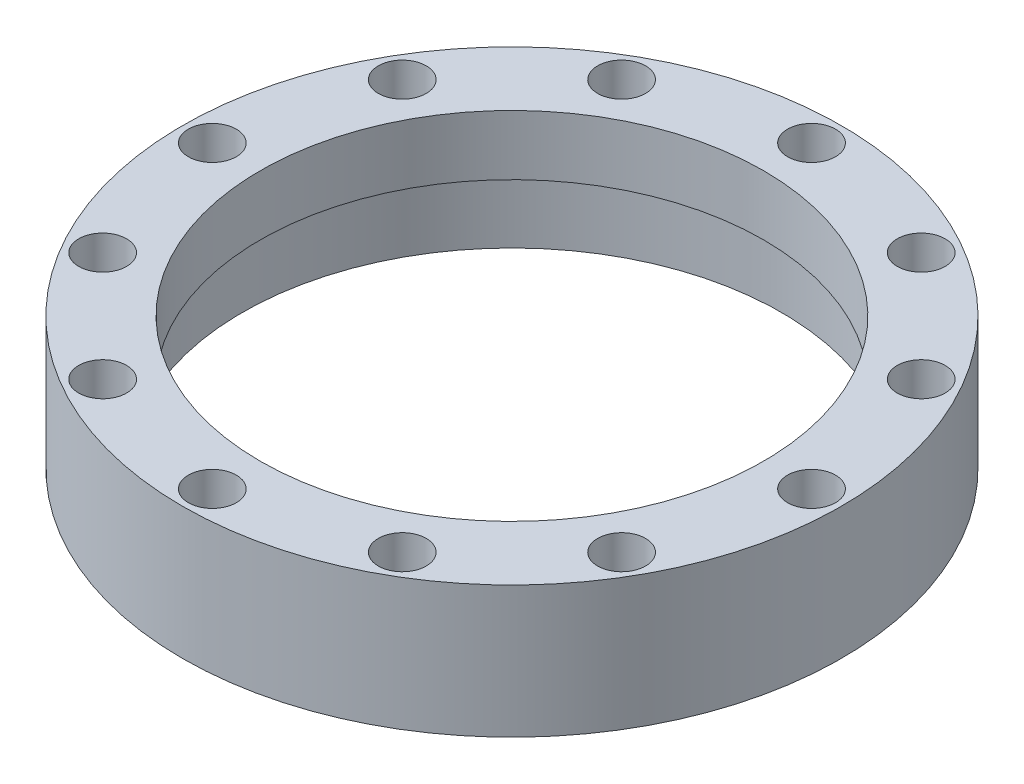
SolidWorks part; units mm, degrees
ref_plane "Front Plane" through (0, 0, 0) normal (0, 0, 1) x (1, 0, 0)
ref_plane "Top Plane" through (0, 0, 0) normal (0, 1, 0) x (1, 0, 0)
ref_plane "Right Plane" through (0, 0, 0) normal (1, 0, 0) x (0, 0, -1)
sketch "Sketch1" plane through (0, 0, 0) normal (0, 1, 0) x (1, 0, 0)
  line L0 (0, 48.2621) -> (0, -49.945) construction
  circle A0 centre (0, 0) radius 27.5
  circle A1 centre (0, 0) radius 25 construction
  circle A2 centre (0, 0) radius 22.5
  circle A3 centre (0, 25) radius 1.5
  circle A4 centre (12.5, 21.6506) radius 1.5
  circle A5 centre (21.6506, 12.5) radius 1.5
  circle A6 centre (25, 0) radius 1.5
  circle A7 centre (21.6506, -12.5) radius 1.5
  circle A8 centre (12.5, -21.6506) radius 1.5
  circle A9 centre (0, -25) radius 1.5
  circle A10 centre (-12.5, -21.6506) radius 1.5
  circle A11 centre (-21.6506, -12.5) radius 1.5
  circle A12 centre (-25, 0) radius 1.5
  circle A13 centre (-21.6506, 12.5) radius 1.5
  circle A14 centre (-12.5, 21.6506) radius 1.5
  point P31 (0, 0)
  point P32 (0, 0)
  dimension "D1" = 55
  dimension "D2" = 50
  dimension "D3" = 45
  dimension "D4" = 3
  dimension "D5" = 12
extrude "Boss-Extrude1" add sketch "Sketch1" along normal blind 11
sketch "Sketch2" plane through (0, 11, 0) normal (0, 1, 0) x (1, 0, 0)
  circle A0 centre (0, 0) radius 22.5
  circle A1 centre (0, 0) radius 21
  dimension "D1" = 42
extrude "Boss-Extrude2" add sketch "Sketch2" against normal blind 5
sketch "Sketch3" plane through (0, 11, 0) normal (0, 1, 0) x (1, 0, 0)
  circle A0 centre (0, 25) radius 2
  circle A1 centre (12.5, 21.6506) radius 2
  circle A2 centre (21.6506, 12.5) radius 2
  circle A3 centre (25, 0) radius 2
  circle A4 centre (21.6506, -12.5) radius 2
  circle A5 centre (12.5, -21.6506) radius 2
  circle A6 centre (0, -25) radius 2
  circle A7 centre (-12.5, -21.6506) radius 2
  circle A8 centre (-21.6506, -12.5) radius 2
  circle A9 centre (-25, 0) radius 2
  circle A10 centre (-21.6506, 12.5) radius 2
  circle A11 centre (-12.5, 21.6506) radius 2
  point P28 (0, 0)
  dimension "D1" = 4
  dimension "D2" = 12
extrude "Cut-Extrude1" cut sketch "Sketch3" against normal blind 5
